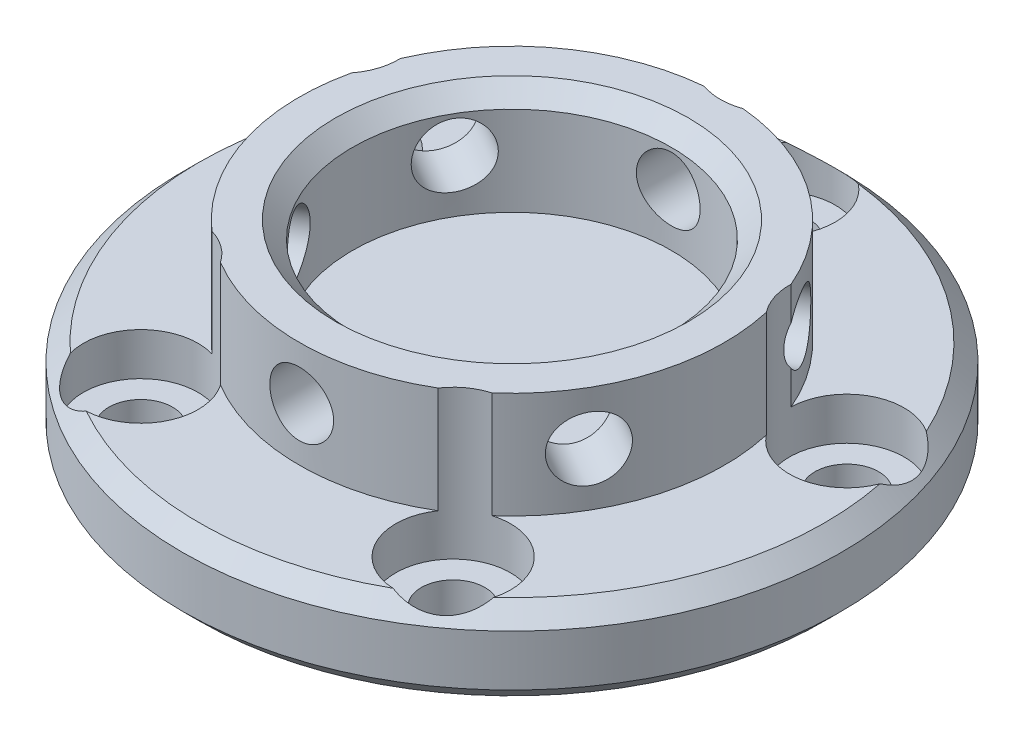
SolidWorks part; units mm, degrees
ref_plane "前视基准面" through (0, 0, 0) normal (0, 0, 1) x (1, 0, 0)
ref_plane "上视基准面" through (0, 0, 0) normal (0, 1, 0) x (1, 0, 0)
ref_plane "右视基准面" through (0, 0, 0) normal (1, 0, 0) x (0, 0, -1)
other "Configuration Table"
sketch "草图1" plane through (0, 0, 0) normal (0, 1, 0) x (1, 0, 0)
  circle A0 centre (0, 0) radius 12.5 construction
  circle A1 centre (0, 12.5) radius 1.5
  circle A2 centre (0, 0) radius 15.5
  circle A3 centre (11.8882, 3.8627) radius 1.5
  circle A4 centre (7.3473, -10.1127) radius 1.5
  circle A5 centre (-7.3473, -10.1127) radius 1.5
  circle A6 centre (-11.8882, 3.8627) radius 1.5
  point P18 (0, 0)
  dimension "D1" = 25
  dimension "D2" = 3
  dimension "D3" = 31
  dimension "D4" = 5
extrude "凸台-拉伸1" add sketch "草图1" along normal blind 4
sketch "草图2" plane through (0, 4, 0) normal (0, 1, 0) x (1, 0, 0)
  circle A0 centre (0, 0) radius 7.5
  circle A1 centre (0, 0) radius 10
  dimension "D1" = 15
  dimension "D2" = 20
extrude "凸台-拉伸2" add sketch "草图2" along normal blind 5
ref_plane "基准面1" through (0, 2, 0) normal (0, 1, 0) x (1, 0, 0)
sketch "草图5" plane through (0, 2, 0) normal (0, 1, 0) x (1, 0, 0)
  circle A0 centre (0, 12.5) radius 2.7
  circle A1 centre (11.8882, 3.8627) radius 2.7
  circle A2 centre (7.3473, -10.1127) radius 2.7
  circle A3 centre (-7.3473, -10.1127) radius 2.7
  circle A4 centre (-11.8882, 3.8627) radius 2.7
  point P14 (0, 0)
  dimension "D1" = 5
extrude "切除-拉伸3" cut sketch "草图5" along normal through all
sketch "草图6" plane through (0, 0, 0) normal (0, 0, 1) x (1, 0, 0)
  line L0 (0, 12.3571) -> (0, -3.1552) construction
  line L1 (10, 6.5) -> (-10, 6.5) construction
  line L2 (10, 4) -> (10, 9) construction
  line L3 (-10, 9) -> (-10, 4) construction
  line L4 (0, 9) -> (0, 4) construction
  circle A0 centre (0, 6.5) radius 1.5
  point P11 (0, 6.5)
  dimension "D1" = 3
extrude "切除-拉伸4" cut sketch "草图6" against normal mid plane 40
pattern_circular "阵列(圆周)2" count 3 every 120 about axis through (0, 9, 0) along (0, 1, 0) of "切除-拉伸4"
chamfer "倒角1" distance 0.8 angle 45 3 edges at (0, 0, 15.5) (0, 4, 15.5) (0, 9, 7.5)
